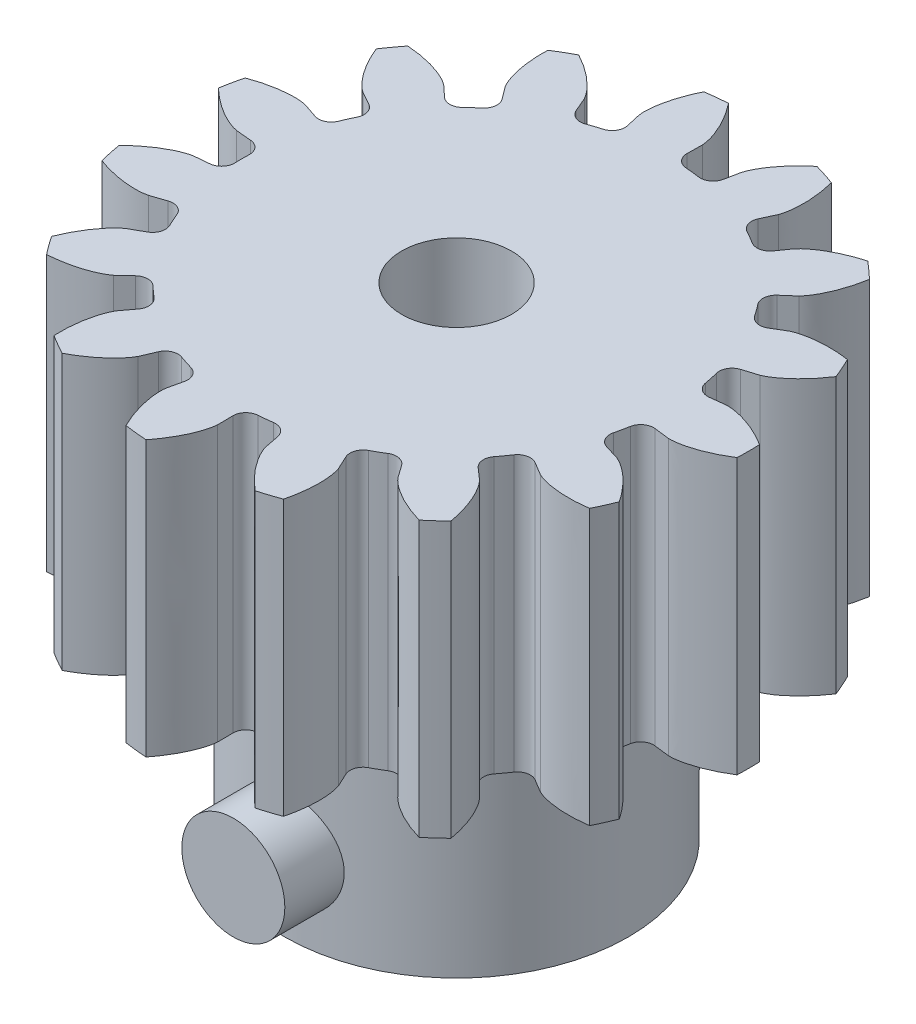
SolidWorks part; units mm, degrees
material "AISI 321 Annealed Stainless Steel (SS)"
ref_plane "Front Plane" through (0, 0, 0) normal (0, 0, 1) x (1, 0, 0)
ref_plane "Top Plane" through (0, 0, 0) normal (0, 1, 0) x (1, 0, 0)
ref_plane "Right Plane" through (0, 0, 0) normal (1, 0, 0) x (0, 0, -1)
sketch "Sketch1" plane through (0, 0, 8) normal (0, -1, 0) x (1, 0, 0)
  line L0 (6.5671, -8.7894) -> (7.0134, -8.8423)
  line L1 (7.0134, -7.1577) -> (6.5671, -7.2106)
  line L2 (6.3204, -6.05) -> (6.7496, -5.9168)
  line L3 (6.0645, -4.378) -> (5.6783, -4.6078)
  line L4 (4.9809, -3.6479) -> (5.3188, -3.3516)
  line L5 (4.0669, -2.2245) -> (3.8076, -2.5915)
  line L6 (2.7801, -1.9982) -> (2.9683, -1.5902)
  line L7 (1.3662, -1.0696) -> (1.2786, -1.5104)
  line L8 (0.0986, -1.3864) -> (0.1046, -0.937)
  line L9 (-1.5707, -1.1131) -> (-1.4715, -1.5514)
  line L10 (-2.6, -1.918) -> (-2.7773, -1.5051)
  line L11 (-4.2361, -2.3474) -> (-3.9672, -2.7074)
  line L12 (-4.8489, -3.5013) -> (-5.1789, -3.1962)
  line L13 (-6.169, -4.559) -> (-5.7769, -4.7786)
  line L14 (-6.2595, -5.8625) -> (-6.685, -5.718)
  line L15 (-7.0352, -7.3657) -> (-6.5877, -7.4067)
  line L16 (-6.5877, -8.5933) -> (-7.0352, -8.6343)
  line L17 (-6.685, -10.282) -> (-6.2595, -10.1375)
  line L18 (-5.7769, -11.2214) -> (-6.169, -11.441)
  line L19 (-5.1789, -12.8038) -> (-4.8489, -12.4987)
  line L20 (-3.9672, -13.2926) -> (-4.2361, -13.6526)
  line L21 (-2.7773, -14.4949) -> (-2.6, -14.082)
  line L22 (-1.4715, -14.4486) -> (-1.5707, -14.8869)
  line L23 (0.1046, -15.063) -> (0.0986, -14.6136)
  line L24 (1.2786, -14.4896) -> (1.3662, -14.9304)
  line L25 (2.9683, -14.4098) -> (2.7801, -14.0018)
  line L26 (3.8076, -13.4085) -> (4.0669, -13.7755)
  line L27 (5.3188, -12.6484) -> (4.9809, -12.3521)
  line L28 (5.6783, -11.3922) -> (6.0645, -11.622)
  line L29 (6.7496, -10.0832) -> (6.3204, -9.95)
  arc A0 (6.0668, -9.5021) -> (6.1533, -9.0954) centre (0, -8) ccw
  arc A1 (6.1533, -9.0954) -> (6.5671, -8.7894) centre (6.5224, -9.1617) cw
  arc A2 (8.4936, -8.3269) -> (8.4936, -7.6731) centre (-0.0001, -8) ccw
  arc A3 (6.5671, -7.2106) -> (6.1533, -6.9046) centre (6.5224, -6.8383) cw
  arc A4 (6.1533, -6.9046) -> (6.0668, -6.4979) centre (0, -8) ccw
  arc A5 (6.0668, -6.4979) -> (6.3204, -6.05) centre (6.431, -6.4084) cw
  arc A6 (7.8923, -4.844) -> (7.6263, -4.2467) centre (-0.0001, -8) ccw
  arc A7 (5.6783, -4.6078) -> (5.1758, -4.4966) centre (5.486, -4.2859) cw
  arc A8 (5.1758, -4.4966) -> (4.9314, -4.1602) centre (0, -8) ccw
  arc A9 (4.9314, -4.1602) -> (4.9809, -3.6479) centre (5.2276, -3.9303) cw
  arc A10 (5.9263, -1.9068) -> (5.4404, -1.4692) centre (-0.0001, -8.0001) ccw
  arc A11 (3.8076, -2.5915) -> (3.3033, -2.6943) centre (3.501, -2.3756) cw
  arc A12 (3.3033, -2.6943) -> (2.9432, -2.4864) centre (0, -8) ccw
  arc A13 (2.9432, -2.4864) -> (2.7801, -1.9982) centre (3.1203, -2.1558) cw
  arc A14 (2.9356, -0.0231) -> (2.3137, 0.179) centre (0, -8.0001) ccw
  arc A15 (1.2786, -1.5104) -> (0.8597, -1.8094) centre (0.9107, -1.4379) cw
  arc A16 (0.8597, -1.8094) -> (0.4462, -1.7659) centre (0, -8) ccw
  arc A17 (0.4462, -1.7659) -> (0.0986, -1.3864) centre (0.4735, -1.3919) cw
  arc A18 (-0.5627, 0.4813) -> (-1.213, 0.4129) centre (0, -8.0001) ccw
  arc A19 (-1.4715, -1.5514) -> (-1.7326, -1.9949) centre (-1.8371, -1.6348) cw
  arc A20 (-1.7326, -1.9949) -> (-2.128, -2.1234) centre (0, -8) ccw
  arc A21 (-2.128, -2.1234) -> (-2.6, -1.918) centre (-2.2551, -1.7706) cw
  arc A22 (-3.9637, -0.4808) -> (-4.53, -0.8078) centre (0, -8.0001) ccw
  arc A23 (-3.9672, -2.7074) -> (-4.0252, -3.2188) centre (-4.2672, -2.9323) cw
  arc A24 (-4.0252, -3.2188) -> (-4.3343, -3.497) centre (0, -8) ccw
  arc A25 (-4.3343, -3.497) -> (-4.8489, -3.5013) centre (-4.5939, -3.2264) cw
  arc A26 (-6.6793, -2.7431) -> (-7.0637, -3.2721) centre (0.0001, -8) ccw
  arc A27 (-5.7769, -4.7786) -> (-5.6219, -5.2694) centre (-5.9595, -5.1061) cw
  arc A28 (-5.6219, -5.2694) -> (-5.7911, -5.6492) centre (0, -8) ccw
  arc A29 (-5.7911, -5.6492) -> (-6.2595, -5.8625) centre (-6.1383, -5.5076) cw
  arc A30 (-8.2401, -5.9143) -> (-8.376, -6.5539) centre (0.0001, -8) ccw
  arc A31 (-6.5877, -7.4067) -> (-6.2465, -7.7921) centre (-6.6214, -7.7802) cw
  arc A32 (-6.2465, -7.7921) -> (-6.2465, -8.2079) centre (0, -8) ccw
  arc A33 (-6.2465, -8.2079) -> (-6.5877, -8.5933) centre (-6.6214, -8.2198) cw
  arc A34 (-8.376, -9.4461) -> (-8.2401, -10.0857) centre (0.0001, -8) ccw
  arc A35 (-6.2595, -10.1375) -> (-5.7911, -10.3508) centre (-6.1383, -10.4924) cw
  arc A36 (-5.7911, -10.3508) -> (-5.6219, -10.7306) centre (0, -8) ccw
  arc A37 (-5.6219, -10.7306) -> (-5.7769, -11.2214) centre (-5.9595, -10.8939) cw
  arc A38 (-7.0637, -12.7279) -> (-6.6793, -13.2569) centre (0.0001, -8) ccw
  arc A39 (-4.8489, -12.4987) -> (-4.3343, -12.503) centre (-4.5939, -12.7736) cw
  arc A40 (-4.3343, -12.503) -> (-4.0252, -12.7812) centre (0, -8) ccw
  arc A41 (-4.0252, -12.7812) -> (-3.9672, -13.2926) centre (-4.2672, -13.0677) cw
  arc A42 (-4.53, -15.1922) -> (-3.9637, -15.5192) centre (0, -7.9999) ccw
  arc A43 (-2.6, -14.082) -> (-2.128, -13.8766) centre (-2.2551, -14.2294) cw
  arc A44 (-2.128, -13.8766) -> (-1.7326, -14.0051) centre (0, -8) ccw
  arc A45 (-1.7326, -14.0051) -> (-1.4715, -14.4486) centre (-1.8371, -14.3652) cw
  arc A46 (-1.213, -16.4129) -> (-0.5627, -16.4813) centre (0, -7.9999) ccw
  arc A47 (0.0986, -14.6136) -> (0.4462, -14.2341) centre (0.4735, -14.6081) cw
  arc A48 (0.4462, -14.2341) -> (0.8597, -14.1906) centre (0, -8) ccw
  arc A49 (0.8597, -14.1906) -> (1.2786, -14.4896) centre (0.9107, -14.5621) cw
  arc A50 (2.3137, -16.179) -> (2.9356, -15.9769) centre (0, -7.9999) ccw
  arc A51 (2.7801, -14.0018) -> (2.9432, -13.5136) centre (3.1203, -13.8442) cw
  arc A52 (2.9432, -13.5136) -> (3.3033, -13.3057) centre (0, -8) ccw
  arc A53 (3.3033, -13.3057) -> (3.8076, -13.4085) centre (3.501, -13.6244) cw
  arc A54 (5.4404, -14.5308) -> (5.9263, -14.0932) centre (-0.0001, -7.9999) ccw
  arc A55 (4.9809, -12.3521) -> (4.9314, -11.8398) centre (5.2276, -12.0697) cw
  arc A56 (4.9314, -11.8398) -> (5.1758, -11.5034) centre (0, -8) ccw
  arc A57 (5.1758, -11.5034) -> (5.6783, -11.3922) centre (5.486, -11.7141) cw
  arc A58 (7.6263, -11.7533) -> (7.8923, -11.156) centre (-0.0001, -8) ccw
  arc A59 (6.3204, -9.95) -> (6.0668, -9.5021) centre (6.431, -9.5916) cw
  spline S0 degree 3 poles (7.0134, -8.8423) (7.1365, -8.8462) (7.2601, -8.8267) (7.3807, -8.8012) (7.5494, -8.7655) (7.7147, -8.712) (7.8746, -8.6473) (8.0899, -8.5601) (8.2972, -8.4511) (8.4936, -8.3269) knots 0 0 0 0 0.00037 0.00037 0.00037 0.000887 0.000887 0.000887 0.001584 0.001584 0.001584 0.001584
  spline S1 degree 3 poles (8.4936, -7.6731) (8.3065, -7.5548) (8.1096, -7.4503) (7.9052, -7.3653) (7.7659, -7.3073) (7.6225, -7.258) (7.4762, -7.221) (7.4011, -7.202) (7.325, -7.1862) (7.2484, -7.1749) (7.1707, -7.1633) (7.0919, -7.1553) (7.0134, -7.1577) knots 0 0 0 0 0.000664 0.000664 0.000664 0.001116 0.001116 0.001116 0.001348 0.001348 0.001348 0.001583 0.001583 0.001583 0.001583
  spline S2 degree 3 poles (6.7496, -5.9168) (6.8637, -5.8703) (6.9687, -5.8023) (7.0685, -5.73) (7.208, -5.6287) (7.3374, -5.5126) (7.457, -5.3885) (7.6183, -5.2212) (7.7633, -5.0373) (7.8923, -4.844) knots 0 0 0 0 0.00037 0.00037 0.00037 0.000887 0.000887 0.000887 0.001584 0.001584 0.001584 0.001584
  spline S3 degree 3 poles (7.6263, -4.2467) (7.4073, -4.2147) (7.1849, -4.1994) (6.9636, -4.2048) (6.8128, -4.2085) (6.6617, -4.2218) (6.513, -4.2475) (6.4366, -4.2607) (6.3608, -4.2772) (6.2862, -4.298) (6.2105, -4.3191) (6.1352, -4.3437) (6.0645, -4.378) knots 0 0 0 0 0.000664 0.000664 0.000664 0.001116 0.001116 0.001116 0.001348 0.001348 0.001348 0.001583 0.001583 0.001583 0.001583
  spline S4 degree 3 poles (5.3188, -3.3516) (5.4041, -3.2627) (5.4724, -3.1579) (5.534, -3.0512) (5.6204, -2.9019) (5.6913, -2.7433) (5.7501, -2.5812) (5.8294, -2.3628) (5.8871, -2.1358) (5.9263, -1.9068) knots 0 0 0 0 0.00037 0.00037 0.00037 0.000887 0.000887 0.000887 0.001584 0.001584 0.001584 0.001584
  spline S5 degree 3 poles (5.4404, -1.4692) (5.2273, -1.5292) (5.0179, -1.6056) (4.8179, -1.7006) (4.6816, -1.7653) (4.549, -1.8389) (4.4236, -1.9229) (4.3593, -1.966) (4.2967, -2.0119) (4.237, -2.0612) (4.1764, -2.1113) (4.1176, -2.1644) (4.0669, -2.2245) knots 0 0 0 0 0.000664 0.000664 0.000664 0.001116 0.001116 0.001116 0.001348 0.001348 0.001348 0.001583 0.001583 0.001583 0.001583
  spline S6 degree 3 poles (2.9683, -1.5902) (3.01, -1.4743) (3.0298, -1.3507) (3.0427, -1.2282) (3.0609, -1.0567) (3.0612, -0.8829) (3.049, -0.7109) (3.0326, -0.4791) (2.993, -0.2483) (2.9356, -0.0231) knots 0 0 0 0 0.00037 0.00037 0.00037 0.000887 0.000887 0.000887 0.001584 0.001584 0.001584 0.001584
  spline S7 degree 3 poles (2.3137, 0.179) (2.1435, 0.0375) (1.9832, -0.1175) (1.8392, -0.2855) (1.741, -0.4001) (1.6498, -0.5213) (1.5694, -0.649) (1.5281, -0.7146) (1.4896, -0.782) (1.4551, -0.8513) (1.4202, -0.9217) (1.3881, -0.9942) (1.3662, -1.0696) knots 0 0 0 0 0.000664 0.000664 0.000664 0.001116 0.001116 0.001116 0.001348 0.001348 0.001348 0.001583 0.001583 0.001583 0.001583
  spline S8 degree 3 poles (0.1046, -0.937) (0.0956, -0.8141) (0.0633, -0.6932) (0.0253, -0.576) (-0.0278, -0.412) (-0.0983, -0.2531) (-0.1794, -0.1009) (-0.2886, 0.1041) (-0.4187, 0.2989) (-0.5627, 0.4813) knots 0 0 0 0 0.00037 0.00037 0.00037 0.000887 0.000887 0.000887 0.001584 0.001584 0.001584 0.001584
  spline S9 degree 3 poles (-1.213, 0.4129) (-1.311, 0.2145) (-1.3943, 0.0077) (-1.4576, -0.2044) (-1.5007, -0.349) (-1.5347, -0.4969) (-1.5562, -0.6462) (-1.5672, -0.7229) (-1.575, -0.8001) (-1.5783, -0.8775) (-1.5816, -0.956) (-1.5814, -1.0353) (-1.5707, -1.1131) knots 0 0 0 0 0.000664 0.000664 0.000664 0.001116 0.001116 0.001116 0.001348 0.001348 0.001348 0.001583 0.001583 0.001583 0.001583
  spline S10 degree 3 poles (-2.7773, -1.5051) (-2.8355, -1.3965) (-2.9141, -1.2992) (-2.9965, -1.2076) (-3.1118, -1.0793) (-3.2407, -0.9628) (-3.3767, -0.8568) (-3.5599, -0.7139) (-3.758, -0.5889) (-3.9637, -0.4808) knots 0 0 0 0 0.00037 0.00037 0.00037 0.000887 0.000887 0.000887 0.001584 0.001584 0.001584 0.001584
  spline S11 degree 3 poles (-4.53, -0.8078) (-4.5388, -1.0289) (-4.5308, -1.2517) (-4.5023, -1.4712) (-4.4828, -1.6209) (-4.4538, -1.7698) (-4.4127, -1.915) (-4.3916, -1.9895) (-4.3673, -2.0632) (-4.3388, -2.1352) (-4.3099, -2.2083) (-4.2775, -2.2806) (-4.2361, -2.3474) knots 0 0 0 0 0.000664 0.000664 0.000664 0.001116 0.001116 0.001116 0.001348 0.001348 0.001348 0.001583 0.001583 0.001583 0.001583
  spline S12 degree 3 poles (-5.1789, -3.1962) (-5.2762, -3.1207) (-5.3876, -3.0637) (-5.5001, -3.0136) (-5.6576, -2.9433) (-5.8228, -2.8893) (-5.9902, -2.8478) (-6.2157, -2.7918) (-6.4475, -2.7581) (-6.6793, -2.7431) knots 0 0 0 0 0.00037 0.00037 0.00037 0.000887 0.000887 0.000887 0.001584 0.001584 0.001584 0.001584
  spline S13 degree 3 poles (-7.0637, -3.2721) (-6.9818, -3.4777) (-6.8839, -3.678) (-6.7685, -3.8669) (-6.6899, -3.9957) (-6.6028, -4.1199) (-6.5062, -4.2358) (-6.4566, -4.2953) (-6.4044, -4.3528) (-6.3491, -4.407) (-6.293, -4.462) (-6.234, -4.5149) (-6.169, -4.559) knots 0 0 0 0 0.000664 0.000664 0.000664 0.001116 0.001116 0.001116 0.001348 0.001348 0.001348 0.001583 0.001583 0.001583 0.001583
  spline S14 degree 3 poles (-6.685, -5.718) (-6.8046, -5.6886) (-6.9296, -5.6819) (-7.0528, -5.6818) (-7.2252, -5.6817) (-7.3981, -5.6995) (-7.5679, -5.7296) (-7.7967, -5.7702) (-8.0221, -5.8337) (-8.2401, -5.9143) knots 0 0 0 0 0.00037 0.00037 0.00037 0.000887 0.000887 0.000887 0.001584 0.001584 0.001584 0.001584
  spline S15 degree 3 poles (-8.376, -6.5539) (-8.2176, -6.7084) (-8.0467, -6.8516) (-7.8644, -6.9773) (-7.7402, -7.0629) (-7.6102, -7.141) (-7.4748, -7.2076) (-7.4053, -7.2418) (-7.3342, -7.273) (-7.2616, -7.3001) (-7.188, -7.3275) (-7.1126, -7.3518) (-7.0352, -7.3657) knots 0 0 0 0 0.000664 0.000664 0.000664 0.001116 0.001116 0.001116 0.001348 0.001348 0.001348 0.001583 0.001583 0.001583 0.001583
  spline S16 degree 3 poles (-7.0352, -8.6343) (-7.1565, -8.6561) (-7.2734, -8.7008) (-7.386, -8.7508) (-7.5435, -8.8209) (-7.6942, -8.9075) (-7.8371, -9.0041) (-8.0296, -9.1341) (-8.2097, -9.2839) (-8.376, -9.4461) knots 0 0 0 0 0.00037 0.00037 0.00037 0.000887 0.000887 0.000887 0.001584 0.001584 0.001584 0.001584
  spline S17 degree 3 poles (-8.2401, -10.0857) (-8.0324, -10.1625) (-7.8181, -10.2237) (-7.6005, -10.2644) (-7.4522, -10.2922) (-7.3016, -10.3106) (-7.1508, -10.3164) (-7.0734, -10.3193) (-6.9958, -10.3189) (-6.9185, -10.3141) (-6.8401, -10.3093) (-6.7613, -10.3008) (-6.685, -10.282) knots 0 0 0 0 0.000664 0.000664 0.000664 0.001116 0.001116 0.001116 0.001348 0.001348 0.001348 0.001583 0.001583 0.001583 0.001583
  spline S18 degree 3 poles (-6.169, -11.441) (-6.2709, -11.5102) (-6.3595, -11.5986) (-6.442, -11.6901) (-6.5575, -11.8181) (-6.6599, -11.9586) (-6.7511, -12.1049) (-6.8741, -12.302) (-6.9777, -12.5121) (-7.0637, -12.7279) knots 0 0 0 0 0.00037 0.00037 0.00037 0.000887 0.000887 0.000887 0.001584 0.001584 0.001584 0.001584
  spline S19 degree 3 poles (-6.6793, -13.2569) (-6.4584, -13.2426) (-6.2377, -13.2114) (-6.0224, -13.1601) (-5.8756, -13.1251) (-5.7306, -13.0807) (-5.5905, -13.0246) (-5.5186, -12.9958) (-5.4478, -12.9639) (-5.3791, -12.9281) (-5.3095, -12.8917) (-5.2409, -12.8519) (-5.1789, -12.8038) knots 0 0 0 0 0.000664 0.000664 0.000664 0.001116 0.001116 0.001116 0.001348 0.001348 0.001348 0.001583 0.001583 0.001583 0.001583
  spline S20 degree 3 poles (-4.2361, -13.6526) (-4.301, -13.7573) (-4.3461, -13.8741) (-4.3842, -13.9912) (-4.4376, -14.1552) (-4.474, -14.3251) (-4.4979, -14.4959) (-4.53, -14.726) (-4.5392, -14.9601) (-4.53, -15.1922) knots 0 0 0 0 0.00037 0.00037 0.00037 0.000887 0.000887 0.000887 0.001584 0.001584 0.001584 0.001584
  spline S21 degree 3 poles (-3.9637, -15.5192) (-3.7677, -15.4162) (-3.5788, -15.2979) (-3.4029, -15.1635) (-3.2831, -15.0718) (-3.1686, -14.9722) (-3.0635, -14.864) (-3.0095, -14.8085) (-2.9578, -14.7506) (-2.9096, -14.6899) (-2.8608, -14.6284) (-2.8144, -14.5641) (-2.7773, -14.4949) knots 0 0 0 0 0.000664 0.000664 0.000664 0.001116 0.001116 0.001116 0.001348 0.001348 0.001348 0.001583 0.001583 0.001583 0.001583
  spline S22 degree 3 poles (-1.5707, -14.8869) (-1.5875, -15.009) (-1.5811, -15.134) (-1.5683, -15.2565) (-1.5504, -15.428) (-1.5145, -15.598) (-1.4669, -15.7638) (-1.4026, -15.9871) (-1.3159, -16.2046) (-1.213, -16.4129) knots 0 0 0 0 0.00037 0.00037 0.00037 0.000887 0.000887 0.000887 0.001584 0.001584 0.001584 0.001584
  spline S23 degree 3 poles (-0.5627, -16.4813) (-0.4255, -16.3075) (-0.301, -16.1226) (-0.1951, -15.9283) (-0.1229, -15.7958) (-0.0588, -15.6583) (-0.0067, -15.5166) (0.02, -15.4439) (0.0436, -15.37) (0.0629, -15.295) (0.0825, -15.2189) (0.0988, -15.1413) (0.1046, -15.063) knots 0 0 0 0 0.000664 0.000664 0.000664 0.001116 0.001116 0.001116 0.001348 0.001348 0.001348 0.001583 0.001583 0.001583 0.001583
  spline S24 degree 3 poles (1.3662, -14.9304) (1.4006, -15.0487) (1.4572, -15.1603) (1.5188, -15.267) (1.6049, -15.4164) (1.7068, -15.5572) (1.8177, -15.6892) (1.9673, -15.867) (2.135, -16.0305) (2.3137, -16.179) knots 0 0 0 0 0.00037 0.00037 0.00037 0.000887 0.000887 0.000887 0.001584 0.001584 0.001584 0.001584
  spline S25 degree 3 poles (2.9356, -15.9769) (2.9902, -15.7624) (3.0288, -15.5428) (3.0465, -15.3222) (3.0586, -15.1718) (3.0612, -15.0201) (3.0511, -14.8695) (3.046, -14.7922) (3.0375, -14.7151) (3.0246, -14.6387) (3.0116, -14.5612) (2.9949, -14.4838) (2.9683, -14.4098) knots 0 0 0 0 0.000664 0.000664 0.000664 0.001116 0.001116 0.001116 0.001348 0.001348 0.001348 0.001583 0.001583 0.001583 0.001583
  spline S26 degree 3 poles (4.0669, -13.7755) (4.1464, -13.8696) (4.2436, -13.9485) (4.3432, -14.021) (4.4827, -14.1225) (4.633, -14.2096) (4.7881, -14.2851) (4.997, -14.3867) (5.2167, -14.4678) (5.4404, -14.5308) knots 0 0 0 0 0.00037 0.00037 0.00037 0.000887 0.000887 0.000887 0.001584 0.001584 0.001584 0.001584
  spline S27 degree 3 poles (5.9263, -14.0932) (5.889, -13.8751) (5.8349, -13.6588) (5.7613, -13.45) (5.7112, -13.3077) (5.6518, -13.1681) (5.5814, -13.0346) (5.5453, -12.9661) (5.5062, -12.8991) (5.4633, -12.8345) (5.4199, -12.7691) (5.3732, -12.7051) (5.3188, -12.6484) knots 0 0 0 0 0.000664 0.000664 0.000664 0.001116 0.001116 0.001116 0.001348 0.001348 0.001348 0.001583 0.001583 0.001583 0.001583
  spline S28 degree 3 poles (6.0645, -11.622) (6.1754, -11.6757) (6.2962, -11.7082) (6.4167, -11.7339) (6.5853, -11.7699) (6.7581, -11.7883) (6.9305, -11.7942) (7.1627, -11.8021) (7.3964, -11.7868) (7.6263, -11.7533) knots 0 0 0 0 0.00037 0.00037 0.00037 0.000887 0.000887 0.000887 0.001584 0.001584 0.001584 0.001584
  spline S29 degree 3 poles (7.8923, -11.156) (7.7694, -10.9719) (7.632, -10.7963) (7.4799, -10.6355) (7.3763, -10.5259) (7.2653, -10.4225) (7.1467, -10.3292) (7.0858, -10.2813) (7.0228, -10.236) (6.9574, -10.1944) (6.8911, -10.1523) (6.8224, -10.1128) (6.7496, -10.0832) knots 0 0 0 0 0.000664 0.000664 0.000664 0.001116 0.001116 0.001116 0.001348 0.001348 0.001348 0.001583 0.001583 0.001583 0.001583
extrude "Boss-Extrude1" add sketch "Sketch1" against normal blind 4 and the other way blind 4
sketch "Sketch2" plane through (0, -4, 0) normal (0, -1, 0) x (-1, 0, 0)
  circle A0 centre (0, 0) radius 5
  dimension "D1" = 10
extrude "Boss-Extrude2" add sketch "Sketch2" along normal blind 6
sketch "Sketch3" plane through (0, -10, 0) normal (0, -1, 0) x (-1, 0, 0)
  circle A0 centre (0, 0) radius 1.6
  dimension "D1" = 3.2
extrude "Cut-Extrude1" cut sketch "Sketch3" against normal up to next
sketch "Sketch6" plane through (0, 0, 0) normal (0, 0, 1) x (1, 0, 0)
  circle A0 centre (0, -7.75) radius 1.5
  dimension "D1" = 3
  dimension "D2" = 7.75
extrude "Boss-Extrude3" add sketch "Sketch6" along normal blind 2 from offset 4.5
